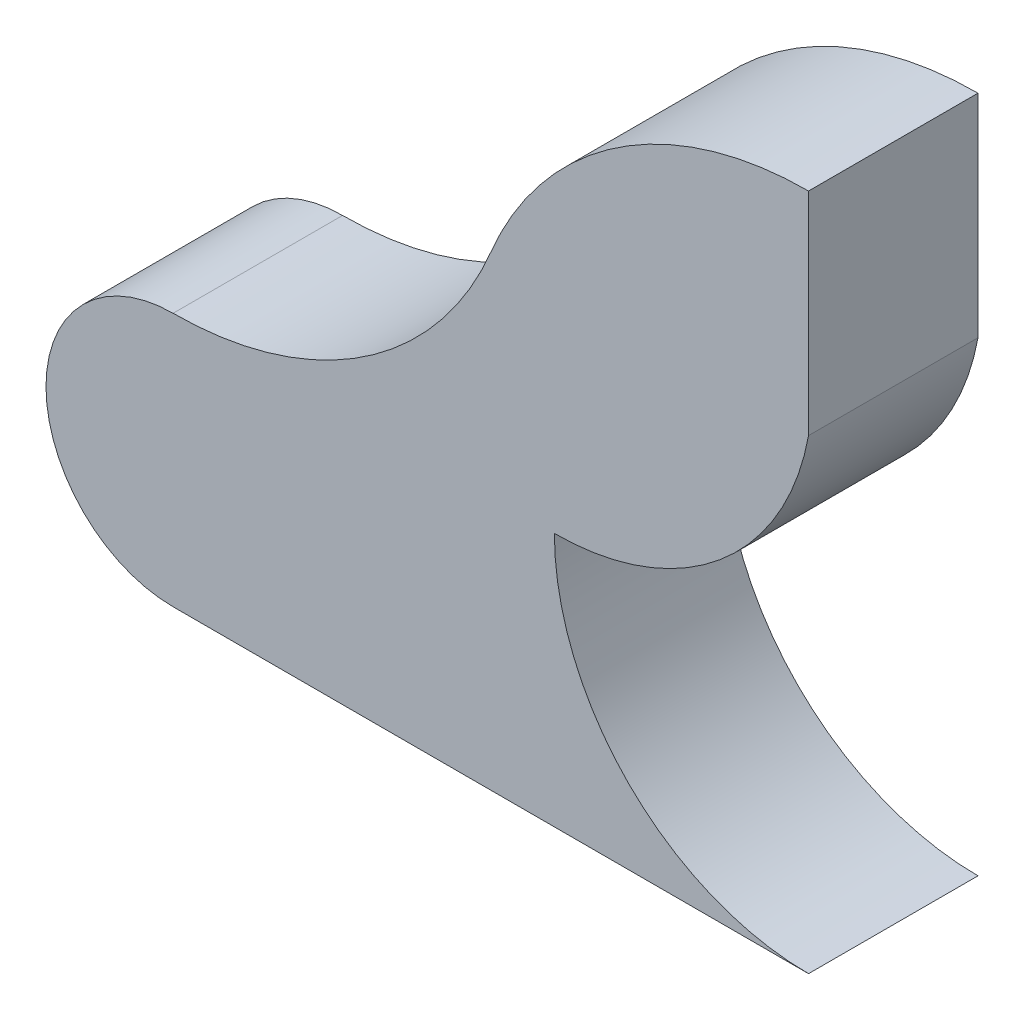
SolidWorks part; units mm, degrees
material "ABS PC"
ref_plane "Front Plane" through (0, 0, 0) normal (0, 0, 1) x (1, 0, 0)
ref_plane "Top Plane" through (0, 0, 0) normal (0, 1, 0) x (1, 0, 0)
ref_plane "Right Plane" through (0, 0, 0) normal (1, 0, 0) x (0, 0, -1)
sketch "Sketch2" plane through (0, 0, 0) normal (0, 0, 1) x (1, 0, 0)
  line L0 (-11.25, 7.5) -> (11.25, 7.5)
  line L1 (11.25, 7.5) -> (11.25, -7.5) construction
  line L2 (11.25, -7.5) -> (-11.25, -7.5)
  line L3 (-11.25, -7.5) -> (-11.25, 7.5) construction
  line L4 (11.25, -7.5) -> (34.1009, -7.5) construction
  line L5 (11.25, -7.5) -> (26.25, -7.5)
  line L6 (26.25, -7.5) -> (26.25, 7.5) construction
  line L7 (26.25, 7.5) -> (11.25, 7.5) construction
  arc A0 (-11.25, 7.5) -> (-11.25, -7.5) centre (-11.25, 0) ccw
  arc A1 (11.25, 7.5) -> (26.25, -7.5) centre (26.25, 7.5) ccw
  point P9 (-18.75, 0)
  point P10 (11.25, 0)
  dimension "D1" = 15
  dimension "D2" = 7.5
  dimension "D3" = 30
  dimension "D4" = 11.25
extrude "Boss-Extrude1" add sketch "Sketch2" against normal blind 10
shell "Shell1" thickness 1 removed face at (1.0983, -0.7767, -10)
sketch "Sketch3" plane through (0, 0, 0) normal (0, 0, 1) x (1, 0, 0)
  line L0 (-18.75, 0) -> (13.2596, 0) construction
  line L1 (13.2596, 0) -> (13.2596, -7.5) construction
  line L2 (-11.25, -7.5) -> (26.25, -7.5) construction
  line L3 (13.2596, -5.5) -> (-11.25, -5.5)
  line L4 (-11.25, -5.5) -> (-11.25, -7.5) construction
  line L5 (-11.25, -7.5) -> (-11.25, 0) construction
  line L6 (-11.25, 0) -> (-11.25, -3.75) construction
  line L7 (-11.25, -3.75) -> (-17.7452, -3.75) construction
  line L8 (-17.7452, -3.75) -> (-17.7452, 3.75) construction
  line L9 (-17.7452, 3.75) -> (-11.25, 3.75) construction
  line L10 (-11.25, 3.75) -> (-11.25, 7.5) construction
  line L11 (-11.25, 7.5) -> (-11.25, 0) construction
  line L12 (13.2596, -5.5) -> (13.2596, -6.569)
  line L14 (-11.25, -6.5) -> (-11.25, -5.5)
  line L16 (-11.25, -6.5) -> (-11.25, -7.5)
  line L17 (-11.25, -7.5) -> (13.2596, -7.5)
  line L18 (13.2596, -7.5) -> (13.2596, -6.569)
  arc A0 (-11.25, 7.5) -> (-11.25, -7.5) centre (-11.25, 0) ccw construction
  arc A1 (11.25, 7.5) -> (26.25, -7.5) centre (26.25, 7.5) ccw construction
  dimension "D1" = 2
extrude "Boss-Extrude2" add sketch "Sketch3" against normal blind 10
sketch "Sketch4" plane through (0, -5.5, 0) normal (0, 1, 0) x (1, 0, 0)
  line L0 (0, 0) -> (0, 10) construction
  line L1 (11.25, 10) -> (-11.25, 10) construction
  line L2 (-11.25, 5) -> (11.25, 5) construction
  line L3 (-11.25, 10) -> (-11.25, 0) construction
  line L4 (11.25, 10) -> (11.25, 0) construction
  point P11 (0, 0)
sketch "Sketch6" plane through (0, 0, -10) normal (0, 0, -1) x (-1, 0, 0)
  line L0 (11.25, 7.5) -> (11.25, 32.5) construction
  line L1 (11.25, 32.5) -> (-26.25, 32.5) construction
  line L2 (-26.25, 32.5) -> (-26.25, -7.5) construction
  line L3 (-26.25, -7.5) -> (-26.25, 7.5) construction
  line L4 (-26.25, 7.5) -> (-11.25, 7.5) construction
  line L5 (11.25, 20) -> (-26.25, 20) construction
  line L6 (-11.25, 7.5) -> (-26.25, 20) construction
  line L7 (11.25, 7.5) -> (-7.5, 32.5) construction
  line L8 (-26.25, 20) -> (-26.25, 32.5)
  line L9 (-11.25, 7.5) -> (11.25, 7.5)
  arc A0 (11.25, 7.5) -> (-7.5, 20) centre (11.25, 27.8125) cw
  arc A1 (-7.5, 20) -> (-26.25, 32.5) centre (-26.25, 12.1875) ccw
  arc A2 (-11.25, 7.5) -> (-26.25, 20) centre (-11.25, 22.75) cw
  dimension "D1" = 40
extrude "Boss-Extrude3" add sketch "Sketch6" against normal blind 10
shell "Shell3" thickness 1 removed face at (9.5223, 9.5254, -10)
